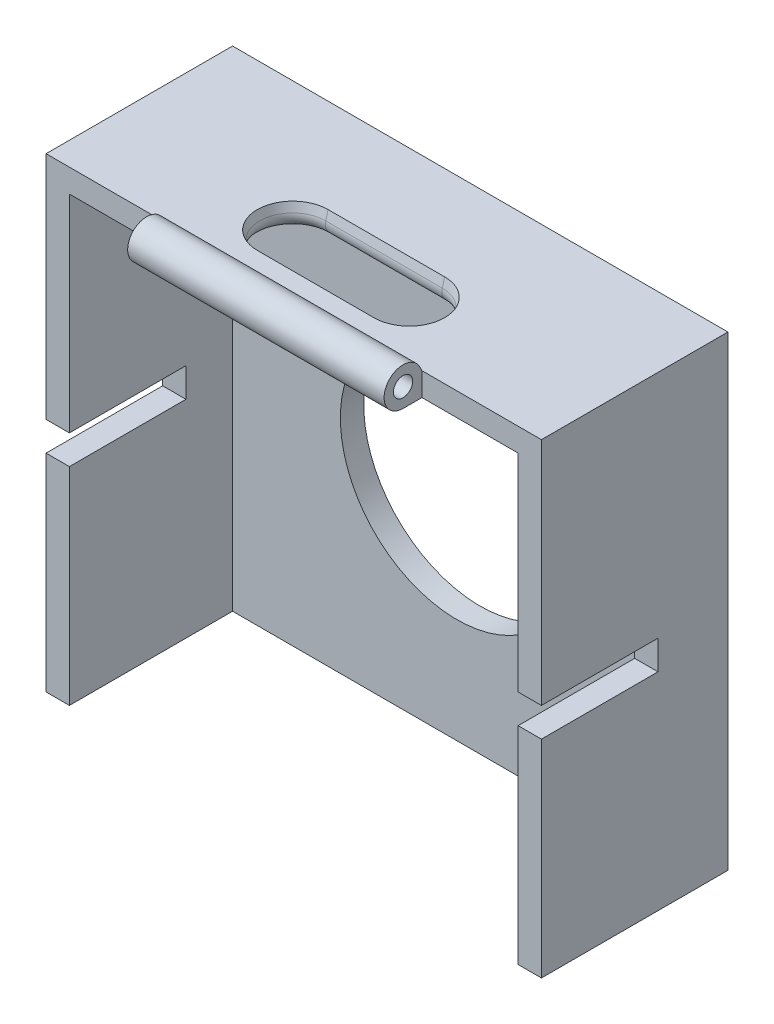
SolidWorks part; units mm, degrees
ref_plane "Front Plane" through (0, 0, 0) normal (0, 0, 1) x (1, 0, 0)
ref_plane "Top Plane" through (0, 0, 0) normal (0, 1, 0) x (1, 0, 0)
ref_plane "Right Plane" through (0, 0, 0) normal (1, 0, 0) x (0, 0, -1)
sketch "Sketch1" plane through (0, 0, 0) normal (0, 0, 1) x (1, 0, 0)
  line L1 (-19.25, 19) -> (19.25, 19)
  line L2 (-19.25, 19) -> (-19.25, -19)
  line L3 (-19.25, -19) -> (19.25, -19)
  line L4 (19.25, 19) -> (19.25, -19)
  line L5 (-19.25, 19) -> (19.25, -19) construction
  line L6 (-19.25, -19) -> (19.25, 19) construction
  circle A0 centre (0, 0) radius 10
  point P0 (0, 0)
  dimension "D3" = 20
  dimension "D1" = 38.5
  dimension "D2" = 38
extrude "Boss-Extrude1" add sketch "Sketch1" along normal blind 2 contours L1 L2 L3 | L1 L3 A0 | L1 L3 L4 | L1 region at (0, 18.4591, 0)
sketch "Sketch2" plane through (0, 0, 2) normal (0, 0, 1) x (1, 0, 0)
  line L0 (-19.25, -19) -> (-21.25, -19)
  line L1 (-21.25, -19) -> (-21.25, 21)
  line L2 (-21.25, 21) -> (21.25, 21)
  line L4 (19.25, -19) -> (21.25, -19)
  line L6 (19.25, -19) -> (19.25, 19)
  line L7 (19.25, 19) -> (-19.25, 19)
  line L8 (0, 40.5) -> (0, -19) construction
  line L9 (-19.25, 19) -> (-19.25, -19)
  line L10 (-19.25, -19) -> (19.25, -19) construction
  line L11 (-19.25, -19) -> (19.25, -19)
  line L12 (19.25, -19) -> (19.25, 19)
  line L13 (19.25, 19) -> (-19.25, 19)
  line L14 (-19.25, 19) -> (-19.25, -19)
  line L15 (-19.25, -19) -> (19.25, -19)
  line L16 (21.25, -19) -> (21.25, 21)
  point P10 (0, 21)
  line M17 (19.25, -19) -> (19.25, 19)
  line M18 (19.25, 19) -> (-19.25, 19)
  line M22 (19.25, 19) -> (-19.25, 19)
  line M23 (-19.25, 19) -> (-19.25, -19)
  dimension "D1" = 0
  dimension "D2" = 2
  dimension "D3" = 2
extrude "Boss-Extrude2" add sketch "Sketch2" along normal blind 14 and the other way up to surface (2 mm away) contours L8 M23 M22 | L8 M18 M17 region at (-20.25, -18.4164, 2) other way up to face at (10, 0, 0)
sketch "Sketch3" plane through (-19.25, 0, 0) normal (1, 0, 0) x (0, 0, -1)
  line L0 (-2, 0) -> (-16, 0) construction
  line L1 (-2, 19) -> (-2, -19) construction
  line L2 (-16, 19) -> (-16, -19) construction
  line L3 (-16, 1.25) -> (-9, 0) construction
  line L4 (-6, 1.25) -> (-16, 1.25)
  line L5 (-6, 1.25) -> (-6, -1.25)
  line L6 (-6, -1.25) -> (-16, -1.25)
  line L7 (-16, 1.25) -> (-16, -1.25)
  line L8 (-9, 0) -> (-16, -1.25) construction
  dimension "D1" = 2.5
  dimension "D2" = 4
extrude "Cut-Extrude1" cut sketch "Sketch3" against normal up to next
ref_plane "Plane1" through (0, 0, 0) normal (1, 0, 0) x (0, 0, -1)
mirror "Mirror1" about plane through (0, 0, 0) normal (1, 0, 0) of "Cut-Extrude1"
sketch "Sketch5" plane through (0, 19, 0) normal (0, -1, 0) x (1, 0, 0)
  line L0 (-5, 11.091) -> (5, 11.091) construction
  line L1 (0, -51757.809) -> (0, 51777.035) construction
  line L2 (-5, 13.591) -> (5, 13.591)
  line L3 (-5, 8.591) -> (5, 8.591)
  arc A0 (-5, 13.591) -> (-5, 8.591) centre (-5, 11.091) ccw
  arc A1 (5, 8.591) -> (5, 13.591) centre (5, 11.091) ccw
  circle A2 centre (0, 11.091) radius 1.218 construction
  point P4 (0, 11.091)
  dimension "D1" = 10
  dimension "D2" = 5
extrude "Cut-Extrude2" cut sketch "Sketch5" against normal through all draft 15 draft outward yes
fillet "Fillet1" radius 1 4 edges at (-7.5, 19, 11.091) (0, 19, 13.591) (7.5, 19, 11.091) (0, 19, 8.591)
sketch "Sketch7" plane through (0, 0, 0) normal (1, 0, 0) x (0, 0, -1)
  line L2 (-16, 19) -> (-22.1271, 19) construction
  line L3 (-16, 1.25) -> (-16, 21) construction
  line L4 (0, 21) -> (-16, 21) construction
  line L5 (-17.625, 19) -> (-16, 19)
  line L6 (-16, 19) -> (-16, 21)
  circle A0 centre (-17.625, 20.625) radius 0.825
  arc A1 (-16.1425, 21.2904) -> (-17.625, 19) centre (-17.625, 20.625) ccw
  arc A2 (-16, 21) -> (-16.1425, 21.2904) centre (-11.8288, 23.2267) cw
  dimension "D1" = 1.65
  dimension "D2" = 3.25
  dimension "D3" = 2
  dimension "D4" = 1.625
extrude "Boss-Extrude3" add sketch "Sketch7" along normal blind 11 and the other way blind 11
